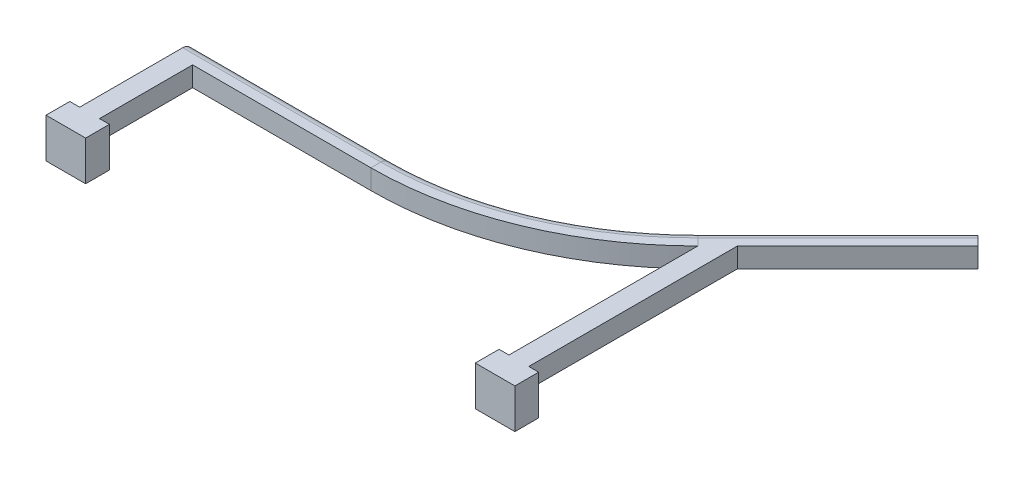
SolidWorks part; units mm, degrees
ref_plane "Front" through (0, 0, 0) normal (0, 0, 1) x (1, 0, 0)
ref_plane "Top" through (0, 0, 0) normal (0, 1, 0) x (1, 0, 0)
ref_plane "Right" through (0, 0, 0) normal (1, 0, 0) x (0, 0, -1)
sketch "Sketch1" plane through (0, 0, 0) normal (0, 1, 0) x (1, 0, 0)
  line L0 (0, 0) -> (50, 0)
  line L1 (106.5685, 23.4315) -> (141.9239, 58.7868)
  arc A0 (50, 0) -> (106.5685, 23.4315) centre (50, 80) ccw
  point P4 (0, 0)
  dimension "D2" = 80
  dimension "D1" = 45
  dimension "D3" = 50
  dimension "D4" = 50
sketch "Sketch2" plane through (0, 0, 0) normal (1, 0, 0) x (0, 0, -1)
  line L1 (-2.5, 2.5) -> (2.5, 2.5)
  line L2 (-2.5, 2.5) -> (-2.5, -2.5)
  line L3 (-2.5, -2.5) -> (2.5, -2.5)
  line L4 (2.5, 2.5) -> (2.5, -2.5)
  point P4 (0, 2.5)
  point P6 (-2.5, 0)
  dimension "D1" = 5
sweep "Sweep3" add profiles "Sketch2" path "Sketch1"
fillet "Fillet1" radius 2.5 6 edges at (122.4784, -2.5, -42.8769) (79.658, -2.5, -8.3993) (122.4784, 2.5, -42.8769) (79.658, 2.5, -8.3993) (25, -2.5, -2.5) (25, 2.5, -2.5)
sketch "Sketch3" plane through (0, 0, 0) normal (0, 1, 0) x (1, 0, 0)
  line L0 (0, -2.5) -> (0, -32)
  line L1 (0, -32) -> (5, -32)
  line L2 (5, -32) -> (5, -2.5)
  line L3 (0, -2.5) -> (50, -2.5) construction
  line L4 (5, -2.5) -> (0, -2.5)
  line L5 (0, 2.5) -> (50, 2.5) construction
  line L6 (108.3363, 21.6637) -> (113.3363, 26.6637)
  line L7 (108.3363, 21.6637) -> (143.6916, 57.019) construction
  line L8 (113.3363, 26.6637) -> (113.3363, -32)
  line L9 (113.3363, -32) -> (108.3363, -32)
  line L10 (108.3363, -32) -> (108.3363, 21.6637)
  dimension "D1" = 34.5
  dimension "D2" = 5
  dimension "D3" = 5
extrude "Boss-Extrude1" add sketch "Sketch3" along normal mid plane 5
sketch "Sketch4" plane through (0, 0, 32) normal (0, 0, 1) x (1, 0, 0)
  line L1 (-2.5, 2.5) -> (7.5, 2.5)
  line L2 (-2.5, 2.5) -> (-2.5, -7.5)
  line L3 (-2.5, -7.5) -> (7.5, -7.5)
  line L4 (7.5, 2.5) -> (7.5, -7.5)
  line L5 (105.8363, 2.5) -> (115.8363, 2.5)
  line L6 (105.8363, 2.5) -> (105.8363, -7.5)
  line L7 (105.8363, -7.5) -> (115.8363, -7.5)
  line L8 (115.8363, 2.5) -> (115.8363, -7.5)
  line L9 (0, 2.5) -> (5, 2.5) construction
  line L11 (108.3363, 2.5) -> (113.3363, 2.5) construction
  point P10 (2.5, -7.5)
  point P13 (2.5, 2.5)
  point P16 (110.8363, 2.5)
  point P19 (110.8363, 2.5)
  dimension "D1" = 10
  dimension "D2" = 10
  dimension "D3" = 10
  dimension "D4" = 10
extrude "Boss-Extrude2" add sketch "Sketch4" against normal blind 6
